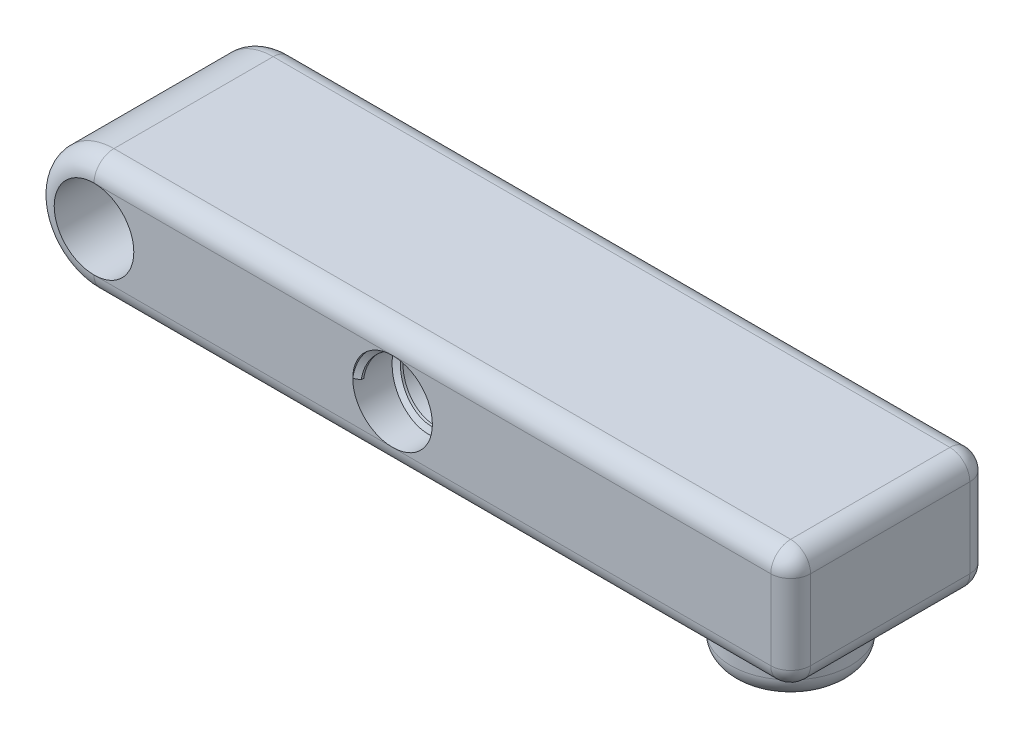
SolidWorks part; units mm, degrees
ref_plane "Front Plane" through (0, 0, 0) normal (0, 0, 1) x (1, 0, 0)
ref_plane "Top Plane" through (0, 0, 0) normal (0, 1, 0) x (1, 0, 0)
ref_plane "Right Plane" through (0, 0, 0) normal (1, 0, 0) x (0, 0, -1)
sketch "Sketch1" plane through (0, 0, 0) normal (0, 0, 1) x (1, 0, 0)
  circle A0 centre (0, 0) radius 15
  circle A1 centre (0, 0) radius 10
  dimension "D1" = 30
  dimension "D2" = 20
extrude "Boss-Extrude1" add sketch "Sketch1" along normal blind 50
ref_plane "Plane1" through (15, 0, 0) normal (1, 0, 0) x (0, 0, -1)
sketch "Sketch2" plane through (0, 0, 0) normal (0, 1, 0) x (1, 0, 0)
  line L0 (0, 0) -> (0, -50)
  line L1 (-15, -50) -> (15, -50) construction
  line L2 (0, -50) -> (175, -50)
  line L3 (175, -50) -> (175, 0)
  line L4 (175, 0) -> (0, 0)
  dimension "D1" = 175
extrude "Boss-Extrude2" add sketch "Sketch2" along normal blind 15 and the other way blind 15
sketch "Sketch3" plane through (0, 0, 50) normal (0, 0, 1) x (1, 0, 0)
  line L0 (0, -10) -> (0, 10) construction
  circle A0 centre (0, 0) radius 10
extrude "Cut-Extrude1" cut sketch "Sketch3" against normal through all both
sketch "Sketch4" plane through (0, -15, 0) normal (0, -1, 0) x (1, 0, 0)
  line L0 (175, 50) -> (175, 0) construction
  line L1 (0, 50) -> (175, 50) construction
  circle A0 centre (150, 25) radius 15
  circle A1 centre (150, 25) radius 10
  dimension "D1" = 30
  dimension "D4" = 20
  dimension "D2" = 25
  dimension "D3" = 25
extrude "Boss-Extrude3" add sketch "Sketch4" along normal blind 15
fillet "Fillet1" radius 5 1 edges at (150, -15, 40)
fillet "Fillet2" radius 5 1 edges at (175, 15, 25)
fillet "Fillet3" radius 5 1 edges at (175, -15, 25)
fillet "Fillet4" radius 5 12 edges at (173.5355, -13.5355, 0) (85, -15, 0) (-15, 0, 0) (85, 15, 0) (173.5355, 13.5355, 0) (173.5355, -13.5355, 50) (85, -15, 50) (-15, 0, 50) (85, 15, 50) (173.5355, 13.5355, 50) (175, 0, 0) (175, 0, 50)
fillet "Fillet5" radius 5 1 edges at (150, -30, 10)
sketch "Sketch6" plane through (0, 0, 50) normal (0, 0, 1) x (1, 0, 0)
  circle A0 centre (75, 0) radius 10
  dimension "D1" = 20
  dimension "D2" = 75
extrude "Cut-Extrude2" cut sketch "Sketch6" against normal blind 52
thread "Thread1" pitch 2.5 method extrude profile "Thread Profile1" start angle 0, offset 0, length 50, pitch 10, diameter 20
ref_plane "Plane2" through (65, 0, 50) normal (0, -1, 0) x (-1, 0, 0)
sketch "Thread Profile1" plane through (65, 0, 50) normal (0, -1, 0) x (-1, 0, 0)
  line L0 (0, 0) -> (0, 2.5) construction
  line L11 (0, 0) -> (0, 2.1875)
  line L12 (0, 2.1875) -> (-1.3532, 1.4062)
  line L13 (-1.3532, 1.4062) -> (-1.3532, 0.7812)
  line L15 (-1.3532, 0.7812) -> (0, 0)
  line L17 (-1.3532, 1.0937) -> (0, 1.0937) construction
  point P2 (0, 0)
  dimension "Pitch" = 2.5
  dimension "Profile_Angle" = 60
  dimension "Profile_Land" = 0.625
  dimension "Profile_Height" = 1.3532
sketch "Sketch9" plane through (175, 0, 0) normal (1, 0, 0) x (0, 0, -1)
  line L0 (0, -10) -> (0, 17.3421)
  line L1 (0, 17.3421) -> (14.0239, 17.3421)
  line L2 (14.0239, 17.3421) -> (14.0239, -16.383)
  line L3 (14.0239, -16.383) -> (0, -16.383)
  line L4 (0, -16.383) -> (0, -10)
  point P4 (14.0239, 17.3421)
extrude "Cut-Extrude3" cut sketch "Sketch9" against normal blind 171
